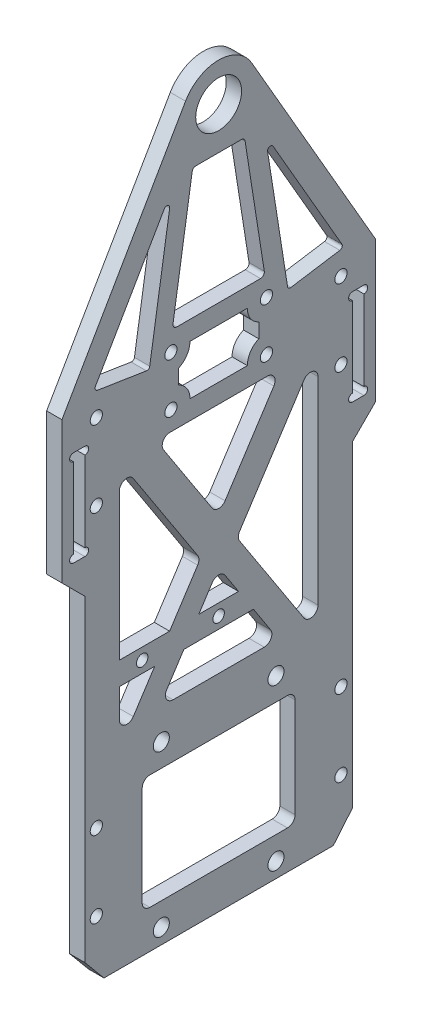
SolidWorks part; units mm, degrees
material "玻纤"
ref_plane "前视基准面" through (0, 0, 0) normal (0, 0, 1) x (1, 0, 0)
ref_plane "上视基准面" through (0, 0, 0) normal (0, 1, 0) x (1, 0, 0)
ref_plane "右视基准面" through (0, 0, 0) normal (1, 0, 0) x (0, 0, -1)
sketch "草图1" plane through (0, 0, 0) normal (1, 0, 0) x (0, 0, -1)
  line L0 (0, 4) -> (60, 4) construction
  line L1 (0, 0) -> (60, 0)
  line L2 (0, 0) -> (0, 50)
  line L3 (0, 50) -> (60, 50)
  line L4 (60, 0) -> (60, 50)
  line L5 (0, 46) -> (60, 46) construction
  line L6 (30, 46) -> (30, 4) construction
  line L7 (15, 46) -> (15, 4) construction
  circle A2 centre (15, 4) radius 2.1
  circle A3 centre (15, 46) radius 2.1
  circle A6 centre (45, 4) radius 2.1
  circle A7 centre (45, 46) radius 2.1
  dimension "D5" = 4.2
  dimension "D6" = 30
  dimension "D1" = 60
  dimension "D2" = 50
  dimension "D3" = 4
  dimension "D4" = 4
extrude "凸台-拉伸1" add sketch "草图1" along normal blind 4
sketch "草图3" plane through (4, 0, 0) normal (1, 0, 0) x (0, 0, -1)
  line L0 (0, 50) -> (-10, 38)
  line L1 (-10, 38) -> (-10, 12)
  line L2 (-10, 12) -> (0, 0)
  line L3 (30, 50) -> (30, 0) construction
  line L4 (60, 50) -> (0, 50) construction
  line L5 (0, 0) -> (60, 0) construction
  line L6 (0, 50) -> (0, 0) construction
  line L7 (70, 12) -> (60, 0)
  line L8 (70, 38) -> (70, 12)
  line L9 (60, 50) -> (70, 38)
  line L10 (0, 50) -> (0, 0)
  line L11 (60, 50) -> (60, 0)
  dimension "D1" = 12
  dimension "D2" = 12
  dimension "D3" = 10
extrude "凸台-拉伸2" add sketch "草图3" against normal blind 4
sketch "草图4" plane through (4, 0, 0) normal (1, 0, 0) x (0, 0, -1)
  line L0 (30, 50) -> (30, 0) construction
  line L1 (60, 50) -> (0, 50) construction
  line L2 (0, 0) -> (60, 0) construction
  line L10 (10, 40) -> (50, 40)
  line L11 (10, 40) -> (10, 10)
  line L12 (10, 10) -> (50, 10)
  line L19 (50, 40) -> (50, 10)
  dimension "D1" = 10
  dimension "D2" = 10
  dimension "D3" = 10
  dimension "D4" = 10
extrude "切除-拉伸2" cut sketch "草图4" against normal blind 4 contours L11 L10 L19 L12
sketch "草图9" plane through (4, 0, 0) normal (1, 0, 0) x (0, 0, -1)
  line L0 (60, 53) -> (0, 53) construction
  line L1 (0, 50) -> (60, 50)
  line L2 (0, 50) -> (0, 133) construction
  line L3 (0, 133) -> (60, 133)
  line L4 (60, 50) -> (60, 133) construction
  line L5 (-5, 50) -> (-5, 44)
  line L6 (0, 50) -> (-5, 50)
  line L7 (0, 50) -> (0, 133) construction
  line L8 (0, 133) -> (-5, 133)
  line L9 (-5, 50) -> (-5, 133)
  line L10 (60, 50) -> (65, 50)
  line L11 (60, 50) -> (60, 133) construction
  line L12 (60, 133) -> (65, 133)
  line L13 (65, 50) -> (65, 133)
  line L18 (-5, 44) -> (0, 50)
  line L19 (0, 50) -> (-10, 38) construction
  line L20 (65, 50) -> (65, 44)
  line L21 (65, 44) -> (60, 50)
  line L22 (70, 38) -> (60, 50) construction
  dimension "D1" = 3
  dimension "D2" = 80
  dimension "D3" = 5
  dimension "D4" = 5
extrude "凸台-拉伸4" add sketch "草图9" against normal blind 4 contours L10 L13 L12 L3 L8 L9 L6 L1 | L5 L18 L6 | L21 L20 L10 region at (4, 91.5, -30) region at (4, 48, 3.3333) region at (4, 48, -63.3333)
sketch "草图10" plane through (4, 0, 0) normal (1, 0, 0) x (0, 0, -1)
  line L0 (-5, 44) -> (-5, 133) construction
  line L1 (-5, 133) -> (-11, 133)
  line L2 (-5, 133) -> (-5, 123)
  line L3 (-5, 123) -> (-11, 123)
  line L4 (-11, 133) -> (-11, 123)
  line L5 (-11, 123) -> (-8, 123)
  line L6 (-11, 123) -> (-11, 88)
  line L7 (-11, 88) -> (-8, 88)
  line L8 (-8, 123) -> (-8, 88)
  line L9 (-8, 88) -> (-5, 88)
  line L10 (-8, 88) -> (-8, 98)
  line L11 (-8, 98) -> (-5, 98)
  line L12 (-5, 88) -> (-5, 98)
  line L13 (30, 133) -> (30, 81.2366)
  line L14 (-5, 133) -> (65, 133) construction
  line L15 (65, 88) -> (65, 98)
  line L16 (68, 98) -> (65, 98)
  line L17 (68, 88) -> (68, 98)
  line L18 (68, 88) -> (65, 88)
  line L19 (68, 123) -> (68, 88)
  line L20 (71, 88) -> (68, 88)
  line L21 (71, 123) -> (71, 88)
  line L22 (71, 123) -> (68, 123)
  line L23 (71, 133) -> (71, 123)
  line L24 (65, 123) -> (71, 123)
  line L25 (65, 133) -> (65, 123)
  line L26 (65, 133) -> (71, 133)
  dimension "D1" = 10
  dimension "D2" = 25
  dimension "D3" = 10
  dimension "D4" = 3
  dimension "D5" = 3
extrude "凸台-拉伸5" add sketch "草图10" against normal blind 4 contours L1 L4 L3 L2 | L8 L3 L6 L7 | L9 L12 L11 L8 | L18 L17 L16 L15 | L21 L22 L19 L17 L20 | L26 L25 L24 L22 L23 region at (4, 128, 8) region at (4, 105.5, 9.5) region at (4, 93, 6.5) region at (4, 93, -66.5) region at (4, 105.5, -69.5) region at (4, 128, -68)
chamfer "倒角1" distance 7 angle 45 2 edges at (2, 88, -71) (2, 88, 11)
sketch "草图11" plane through (0, 0, 0) normal (-1, 0, 0) x (0, 0, 1)
  line L0 (-30, 133) -> (-30, 0) construction
  line L1 (11, 133) -> (-71, 133) construction
  line L2 (0, 0) -> (-60, 0) construction
  line L3 (-56, 108.2598) -> (-56, 56.5)
  line L4 (-52.3237, 55.4091) -> (-35.4823, 81.289)
  line L5 (-35.4823, 83.4708) -> (-52.3237, 109.3507)
  line L6 (-42.7675, 115) -> (-17.2325, 115)
  line L7 (-15.5562, 111.9091) -> (-28.3237, 92.2895)
  line L8 (-31.6763, 92.2895) -> (-44.4438, 111.9091)
  line L9 (-31.6763, 75.4155) -> (-43.6011, 57.0909)
  line L10 (-41.9248, 54) -> (-18.0752, 54)
  line L11 (-16.3989, 57.0909) -> (-28.3237, 75.4155)
  line L12 (-65, 44) -> (-65, 89) construction
  line L13 (-24.5177, 83.4708) -> (-7.6763, 109.3507)
  line L14 (-7.6763, 55.4091) -> (-24.5177, 81.289)
  line L15 (-4, 108.2598) -> (-4, 56.5)
  circle A8 centre (-45, 46) radius 2.1 construction
  arc A10 (-52.3237, 109.3507) -> (-56, 108.2598) centre (-54, 108.2598) ccw
  arc A11 (-28.3237, 92.2895) -> (-31.6763, 92.2895) centre (-30, 93.3804) cw
  arc A12 (-42.7675, 115) -> (-44.4438, 111.9091) centre (-42.7675, 113) ccw
  arc A13 (-17.2325, 115) -> (-15.5562, 111.9091) centre (-17.2325, 113) cw
  arc A14 (-7.6763, 109.3507) -> (-4, 108.2598) centre (-6, 108.2598) cw
  arc A15 (-24.5177, 83.4708) -> (-24.5177, 81.289) centre (-22.8414, 82.3799) ccw
  arc A16 (-7.6763, 55.4091) -> (-4, 56.5) centre (-6, 56.5) ccw
  arc A17 (-18.0752, 54) -> (-16.3989, 57.0909) centre (-18.0752, 56) ccw
  arc A18 (-31.6763, 75.4155) -> (-28.3237, 75.4155) centre (-30, 74.3247) cw
  arc A19 (-43.6011, 57.0909) -> (-41.9248, 54) centre (-41.9248, 56) ccw
  arc A20 (-35.4823, 81.289) -> (-35.4823, 83.4708) centre (-37.1586, 82.3799) ccw
  arc A21 (-56, 56.5) -> (-52.3237, 55.4091) centre (-54, 56.5) ccw
  circle A22 centre (-45, 46) radius 2.1 construction
  point P15 (-30, 115)
  point P16 (-30, 54)
  point P28 (-56, 115)
  point P34 (-30, 89.7135)
  point P37 (-46.4552, 115)
  point P42 (-4, 115)
  point P45 (-25.2276, 82.3799)
  point P48 (-4, 49.7598)
  point P53 (-30, 77.9915)
  point P58 (-34.7724, 82.3799)
  point P61 (-56, 49.7598)
  dimension "D1" = 8
  dimension "D2" = 10.5
  dimension "D7" = 2
  dimension "D3" = 8
  dimension "D6" = 9
  dimension "D5" = 18
extrude "切除-拉伸7" cut sketch "草图11" against normal blind 10 contours L3 A21 L4 A20 L5 A10 | L6 L0 A11 L7 A13 | L0 L6 A12 L8 A11 | L0 A18 L9 A19 L10 | A18 L0 L10 A17 L11 | L14 A16 L15 A14 L13 A15
sketch "草图15" plane through (0, 0, 0) normal (-1, 0, 0) x (0, 0, 1)
  line L0 (11, 133) -> (11, 95) construction
  line L1 (-71, 133) -> (11, 133)
  line L2 (-71, 133) -> (-71, 143)
  line L3 (-71, 143) -> (11, 143)
  line L4 (11, 133) -> (11, 143)
  line L5 (-30, 183) -> (-30, 143) construction
  line L6 (-47.5, 143) -> (-12.5, 143)
  line L7 (-47.5, 143) -> (-47.5, 183)
  line L8 (-47.5, 183) -> (-12.5, 183) construction
  line L9 (-12.5, 143) -> (-12.5, 183)
  circle A0 centre (-30, 183) radius 17.5
  circle A1 centre (-30, 183) radius 6
  dimension "D1" = 10
  dimension "D3" = 35
  dimension "D4" = 12
  dimension "D2" = 50
extrude "凸台-拉伸7" add sketch "草图15" against normal blind 4 contours A0 A1 | A0 L7 L3 L9 | L1 L4 L3 L2 region at (0, 138, -30) region at (0, 156.4183, -30) region at (0, 200.005, -30)
sketch "草图16" plane through (4, 0, 0) normal (1, 0, 0) x (0, 0, -1)
  line L0 (41.9248, 54) -> (18.0752, 54) construction
  line L7 (12.5, 143) -> (-11, 143) construction
  line L8 (30, 183) -> (30, 54)
  line L14 (-5, 98) -> (-5, 123) construction
  circle A0 centre (-2, 128) radius 1.6
  circle A1 centre (-2, 108) radius 1.6
  circle A2 centre (62, 108) radius 1.6
  circle A3 centre (62, 128) radius 1.6
  dimension "D2" = 3.2
  dimension "D3" = 3.2
  dimension "D4" = 15
  dimension "D5" = 20
  dimension "D1" = 3
extrude "切除-拉伸9" cut sketch "草图16" against normal blind 4 contours A0 | A1 | A2 | A3 region at (4, 128, 2) region at (4, 108, 2) region at (4, 108, -62) region at (4, 128, -62)
sketch "草图17" plane through (4, 0, 0) normal (1, 0, 0) x (0, 0, -1)
  line L0 (-11, 143) -> (12.5, 183)
  line L1 (12.5, 183) -> (12.5, 143)
  line L2 (47.5, 183) -> (71, 143)
  line L3 (12.5, 143) -> (-11, 143)
  line L4 (47.5, 183) -> (47.5, 143)
  line L5 (47.5, 143) -> (71, 143)
extrude "凸台-拉伸8" add sketch "草图17" against normal blind 4
sketch "草图21" plane through (4, 0, 0) normal (1, 0, 0) x (0, 0, -1)
  line L0 (68, 123) -> (68, 121)
  line L1 (68, 123) -> (68, 98) construction
  line L2 (68, 98) -> (68, 100)
  line L3 (66.5, 123) -> (66.5, 98) construction
  line L5 (68, 98) -> (65, 98) construction
  line L6 (65, 98) -> (65, 100)
  line L7 (65, 123) -> (65, 121)
  line L8 (65, 123) -> (68, 123) construction
  line L9 (-8, 123) -> (-8, 121)
  line L10 (-8, 123) -> (-8, 98) construction
  line L11 (-8, 98) -> (-8, 100)
  line L12 (-6.5, 123) -> (-6.5, 98) construction
  line L15 (-8, 98) -> (-5, 98) construction
  line L20 (-5, 98) -> (-5, 100)
  line L23 (-5, 123) -> (-5, 121)
  line L24 (-5, 123) -> (-8, 123) construction
  arc A8 (68, 123) -> (68, 121) centre (68, 122) cw
  arc A9 (68, 98) -> (68, 100) centre (68, 99) ccw
  arc A10 (65, 98) -> (65, 100) centre (65, 99) cw
  arc A11 (65, 123) -> (65, 121) centre (65, 122) ccw
  arc A12 (-8, 123) -> (-8, 121) centre (-8, 122) ccw
  arc A17 (-8, 98) -> (-8, 100) centre (-8, 99) cw
  arc A18 (-5, 98) -> (-5, 100) centre (-5, 99) ccw
  arc A19 (-5, 123) -> (-5, 121) centre (-5, 122) cw
  dimension "D1" = 1
extrude "切除-拉伸12" cut sketch "草图21" against normal blind 10
sketch "草图22" plane through (0, 0, 0) normal (-1, 0, 0) x (0, 0, 1)
  line L1 (-42.5, 120) -> (-17.5, 120) construction
  line L2 (-42.5, 120) -> (-42.5, 133) construction
  line L3 (-42.5, 133) -> (-17.5, 133) construction
  line L4 (-17.5, 120) -> (-17.5, 133) construction
  circle A0 centre (-42.5, 133) radius 1.6
  circle A1 centre (-17.5, 133) radius 1.6
  circle A2 centre (-42.5, 120) radius 1.6
  circle A3 centre (-17.5, 120) radius 1.6
  circle A4 centre (-62, 128) radius 1.6 construction
  dimension "D1" = 3.2
  dimension "D3" = 19.5
  dimension "D2" = 8
  dimension "D4" = 25
  dimension "D5" = 13
extrude "切除-拉伸13" cut sketch "草图22" against normal through all
sketch "草图23" plane through (0, 0, 0) normal (-1, 0, 0) x (0, 0, 1)
  line L0 (-38.6597, 188.0009) -> (-71, 132)
  line L1 (-71, 143) -> (-71, 95) construction
  line L2 (-21.3403, 188.0009) -> (11, 132)
  line L3 (11, 143) -> (11, 95) construction
  line L4 (-12.5, 183) -> (11, 143) construction
  line L5 (-71, 143) -> (-47.5, 183) construction
  line L6 (11, 143) -> (11, 132)
  line L7 (-12.5, 183) -> (11, 143)
  line L8 (-71, 143) -> (-71, 132)
  line L9 (-71, 143) -> (-47.5, 183)
  line L10 (-40.5, 128.4174) -> (-40.5, 124.5826)
  line L11 (-37.5, 133) -> (-22.5, 133)
  line L12 (-19.5, 128.4174) -> (-19.5, 124.5826)
  line L13 (-22.5, 120) -> (-37.5, 120)
  line L14 (-39.879, 184.5507) -> (-47.5, 136) construction
  line L15 (-30, 183) -> (-30, 0) construction
  line L16 (0, 0) -> (-60, 0) construction
  line L17 (-42.81, 165.8786) -> (-48.0259, 132.6493)
  line L18 (-20.121, 184.5507) -> (-12.5, 136) construction
  line L19 (-36.9205, 171.1551) -> (-41.9435, 139.1551)
  line L20 (-23.0795, 171.1551) -> (-18.0565, 139.1551)
  line L21 (-40.9556, 138) -> (-19.0444, 138)
  line L22 (-35.9326, 172) -> (-24.0674, 172)
  line L23 (-47.5, 136) -> (-47.5, 120) construction
  line L24 (-48.8947, 132.0163) -> (-61.707, 134.0275)
  line L25 (-62.2474, 135.1585) -> (-44.2191, 166.3766)
  line L26 (-11.1053, 132.0163) -> (1.707, 134.0275)
  line L27 (-17.19, 165.8786) -> (-11.9741, 132.6493)
  line L28 (2.2474, 135.1585) -> (-15.7809, 166.3766)
  arc A0 (-21.3403, 188.0009) -> (-38.6597, 188.0009) centre (-30, 183) ccw
  circle A1 centre (-42.5, 120) radius 1.6 construction
  arc A2 (-12.5, 183) -> (-47.5, 183) centre (-30, 183) ccw construction
  arc A3 (-12.5, 183) -> (-47.5, 183) centre (-30, 183) ccw
  arc A4 (-40.5, 128.4174) -> (-37.5, 133) centre (-42.5, 133) ccw
  arc A5 (-22.5, 133) -> (-19.5, 128.4174) centre (-17.5, 133) ccw
  arc A6 (-22.5, 120) -> (-19.5, 124.5826) centre (-17.5, 120) cw
  arc A7 (-37.5, 120) -> (-40.5, 124.5826) centre (-42.5, 120) ccw
  circle A8 centre (-30, 183) radius 10 construction
  circle A9 centre (-42.5, 133) radius 1.6 construction
  arc A13 (-41.9435, 139.1551) -> (-40.9556, 138) centre (-40.9556, 139) ccw
  arc A14 (-18.0565, 139.1551) -> (-19.0444, 138) centre (-19.0444, 139) cw
  arc A15 (-23.0795, 171.1551) -> (-24.0674, 172) centre (-24.0674, 171) ccw
  arc A16 (-36.9205, 171.1551) -> (-35.9326, 172) centre (-35.9326, 171) cw
  circle A17 centre (-62, 128) radius 1.6 construction
  arc A18 (-48.0259, 132.6493) -> (-48.8947, 132.0163) centre (-48.7768, 132.7672) cw
  arc A19 (-61.707, 134.0275) -> (-62.2474, 135.1585) centre (-61.5892, 134.7784) cw
  arc A20 (-42.81, 165.8786) -> (-44.2191, 166.3766) centre (-43.5609, 165.9965) ccw
  arc A21 (-11.9741, 132.6493) -> (-11.1053, 132.0163) centre (-11.2232, 132.7672) ccw
  arc A22 (1.707, 134.0275) -> (2.2474, 135.1585) centre (1.5892, 134.7784) ccw
  arc A23 (-17.19, 165.8786) -> (-15.7809, 166.3766) centre (-16.4391, 165.9965) cw
  point P47 (-42.1248, 138)
  point P50 (-17.8752, 138)
  point P68 (-42.1767, 169.9132)
  dimension "D1" = 10
  dimension "D3" = 2
  dimension "D5" = 5
  dimension "D6" = 5
  dimension "D7" = 11
  dimension "D11" = 1
  dimension "D15" = 0.7601
  dimension "D2" = 12
  dimension "D4" = 2
  dimension "D8" = 5
  dimension "D9" = 5
  dimension "D10" = 5
  dimension "D12" = 3
  dimension "D13" = 6
  dimension "D14" = 6
extrude "切除-拉伸14" cut sketch "草图23" against normal through all
sketch "草图24" plane through (4, 0, 0) normal (1, 0, 0) x (0, 0, -1)
  line L0 (-5, 44) -> (-5, 6)
  line L1 (-10, 12) -> (0, 0) construction
  line L2 (-5, 6) -> (-10, 12)
  line L3 (-10, 12) -> (-10, 38)
  line L4 (-10, 38) -> (-5, 44)
  line L5 (65, 44) -> (65, 6)
  line L6 (60, 0) -> (70, 12) construction
  line L7 (65, 6) -> (70, 12)
  line L8 (70, 12) -> (70, 38)
  line L9 (70, 38) -> (65, 44)
  line L10 (10, 40) -> (50, 40) construction
  line L11 (10, 10) -> (50, 10) construction
  line L12 (30, 40) -> (30, 10) construction
  circle A0 centre (-2, 35) radius 1.6
  circle A1 centre (-2, 15) radius 1.6
  circle A2 centre (62, 15) radius 1.6
  circle A3 centre (62, 35) radius 1.6
  dimension "D1" = 3.2
  dimension "D2" = 3
  dimension "D3" = 5
  dimension "D4" = 5
extrude "切除-拉伸15" cut sketch "草图24" against normal through all
fillet "圆角1" radius 2 4 edges at (2, 40, -10) (2, 10, -10) (2, 10, -50) (2, 40, -50)
sketch "草图26" plane through (0, 0, 0) normal (-1, 0, 0) x (0, 0, 1)
  line L0 (-35.2005, 70) -> (-4, 70)
  line L1 (-31.6763, 75.4155) -> (-43.6011, 57.0909) construction
  line L2 (-39.105, 64) -> (-4, 64)
  line L3 (-4, 108.2598) -> (-4, 56.5) construction
  line L4 (-41.9248, 54) -> (-18.0752, 54) construction
  line L5 (-39.105, 64) -> (-35.2005, 70)
  line L6 (-4, 64) -> (-4, 70)
  line L7 (-30, 67) -> (-30, 183) construction
  circle A0 centre (-30, 67) radius 1.5
  circle A1 centre (-10, 67) radius 1.5
  dimension "D3" = 3
  dimension "D5" = 3
  dimension "D1" = 10
  dimension "D2" = 6
  dimension "D4" = 20
extrude "凸台-拉伸9" add sketch "草图26" against normal up to surface (4 mm away) up to face at (4, 35, -60.4)
